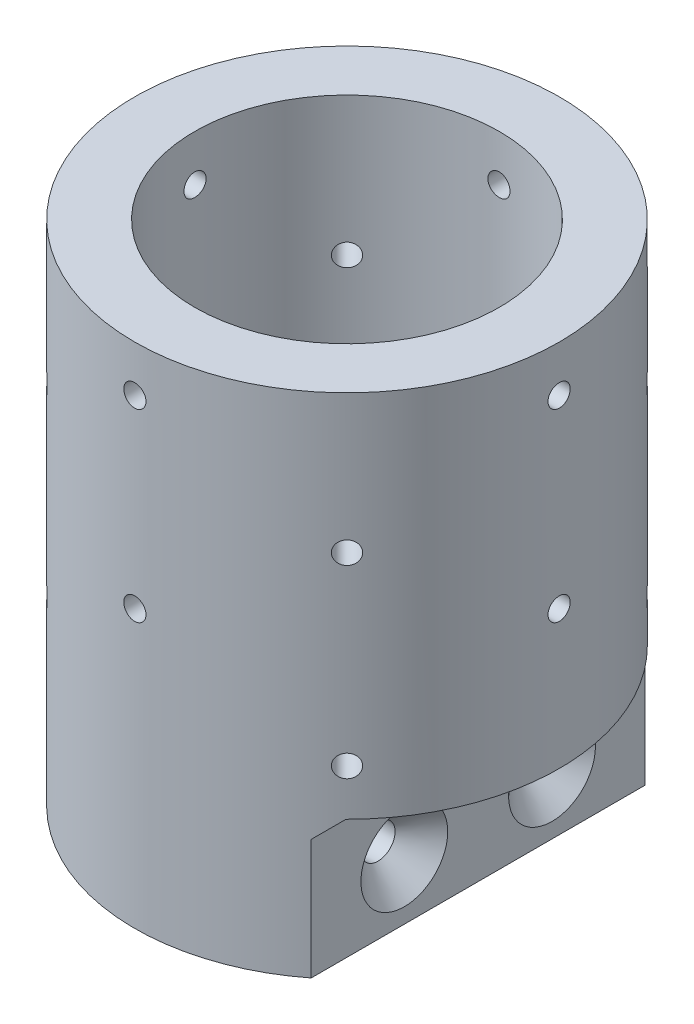
SolidWorks part; units mm, degrees
ref_plane "Спереди" through (0, 0, 0) normal (0, 0, 1) x (1, 0, 0)
ref_plane "Сверху" through (0, 0, 0) normal (0, 1, 0) x (1, 0, 0)
ref_plane "Справа" through (0, 0, 0) normal (1, 0, 0) x (0, 0, -1)
sketch "Эскиз1" plane through (0, 0, 0) normal (0, 1, 0) x (1, 0, 0)
  circle A0 centre (0, 0) radius 23
  dimension "D1" = 46
extrude "Бобышка-Вытянуть1" add sketch "Эскиз1" along normal blind 5
sketch "Эскиз2" plane through (0, 5, 0) normal (0, 1, 0) x (1, 0, 0)
  circle A0 centre (0, 0) radius 23
  circle A1 centre (0, 0) radius 16.5
  circle A2 centre (0, 0) radius 23 construction
  dimension "D1" = 33
  dimension "D2" = 0
extrude "Бобышка-Вытянуть2" add sketch "Эскиз2" along normal blind 35
chamfer "Фаска8" distance 2 angle 45 1 edges at (0, 5, 16.5)
sketch "Эскиз3" plane through (0, 0, 0) normal (1, 0, 0) x (0, 0, -1)
  line L0 (-23, 20) -> (28.0263, 20) construction
  line L1 (-23, 40) -> (-23, 0) construction
  line L2 (16.5, 40) -> (-16.5, 40) construction
  circle A1 centre (0, 35) radius 1.2
  dimension "D1" = 2.4
  dimension "D2" = 5
extrude "Вырез-Вытянуть1" cut sketch "Эскиз3" against normal through all
ref_plane "Плоскость1" through (0, 0, 0) normal (0.7071, 0, 0.7071) x (0, -1, 0)
sketch "Эскиз4" plane through (0, 0, 0) normal (0.7071, 0, 0.7071) x (0, -1, 0)
  line L0 (-20, 23) -> (-20, -30.0625) construction
  line L1 (0, 23) -> (-40, 23) construction
  line L3 (0, -23) -> (0, 23) construction
  circle A1 centre (-5, 0) radius 1.2
  dimension "D1" = 5
  dimension "D2" = 2.4
extrude "Вырез-Вытянуть2" cut sketch "Эскиз4" against normal through all from offset 16.3 offset against normal yes
pattern_circular "Круговой массив1" count 4 over 360 about axis through (0, 5, 0) along (0, -1, 0) of "Вырез-Вытянуть2"
pattern_circular "Круговой массив2" count 4 over 360 about axis through (0, 5, 0) along (0, -1, 0) of "Вырез-Вытянуть1"
pattern_linear "Линейный массив3" count 2 spacing 20 along (0, 1, 0) of "Круговой массив1"
pattern_linear "Линейный массив4" count 2 spacing 20 along (0, -1, 0) of "Круговой массив2"
sketch "Эскиз12" plane through (0, 0, 0) normal (0, -1, 0) x (1, 0, 0)
  line L1 (14.207, 18.0876) -> (14.207, -18.0876)
  line L20 (0, 15) -> (-2.7835, 17.7835)
  line L21 (-2.7835, -17.7835) -> (0, -15)
  line L22 (0, -15) -> (0, 15)
  line L23 (0, 15) -> (-2.7835, 17.7835)
  line L24 (-2.7835, -17.7835) -> (0, -15)
  line L25 (0, -15) -> (0, 15)
  circle A6 centre (0, 0) radius 23 construction
  arc A7 (14.207, 18.0876) -> (14.207, -18.0876) centre (0, 0) ccw
  arc A13 (-2.7835, 17.7835) -> (-2.7835, -17.7835) centre (0, 0) ccw
  arc A14 (-2.7835, 17.7835) -> (-2.7835, -17.7835) centre (0, 0) ccw
  dimension "D1" = 0
extrude "Бобышка-Вытянуть3" add sketch "Эскиз12" along normal blind 15 contours L1 region at (13.6153, 0, 0)
sketch "Эскиз13" plane through (0, -15, 0) normal (0, -1, 0) x (1, 0, 0)
  line L14 (-2.6786, -18.1029) -> (0.3, -15.1243)
  line L15 (0.3, 15.1243) -> (-2.6786, 18.1029)
  line L16 (0.3, -15.1243) -> (0.3, 15.1243)
  line L17 (-2.6786, -18.1029) -> (0.3, -15.1243)
  line L18 (0.3, 15.1243) -> (-2.6786, 18.1029)
  line L19 (0.3, -15.1243) -> (0.3, 15.1243)
  arc A5 (-2.6786, 18.1029) -> (-2.6786, -18.1029) centre (0, 0) ccw
  arc A6 (-2.6786, 18.1029) -> (-2.6786, -18.1029) centre (0, 0) ccw
  dimension "D1" = 0.3
extrude "Вырез-Вытянуть10" cut sketch "Эскиз13" against normal up to surface (15 mm away) up to face at (18.6035, 0, 0)
chamfer "Фаска4" distance 2 angle 45 1 edges at (14.207, 0, 0)
chamfer "Фаска6" distance 2 angle 45 4 edges at (-1.1893, 0, -16.6136) (-18.3, 0, 0) (0.3, 0, 0) (-1.1893, 0, 16.6136)
chamfer "Фаска7" distance 2 angle 45 4 edges at (-1.1893, -15, -16.6136) (-18.3, -15, 0) (-1.1893, -15, 16.6136) (0.3, -15, 0)
hole_wizard "Зенковка для винта с полупотайной головкой M41" positions "Эскиз14" profile "Эскиз15" countersink size "M4" standard "ISO" end condition through all
sketch "Эскиз14" plane through (14.207, -676.2045, -24.0267) normal (1, 0, 0) x (0, 0.0202, -0.9998)
  line L0 (-10.4265, 674.5519) -> (-10.6887, 661.5545) construction
  line L4 (-10.5576, 668.0532) -> (-20.4413, 668.0532) construction
  line L5 (-20.4413, 668.0532) -> (-1.8045, 668.0532) construction
  point P0 (-18.5576, 668.0532)
  point P19 (-2.5641, 667.7306)
sketch "Эскиз15" plane through (14.207, -8.6613, 7.9984) normal (0, 1, 0) x (0, 0, -1)
  line L0 (0, 0) -> (0, 37.207)
  line L1 (0, 37.207) -> (1.85, 37.207)
  line L2 (1.85, 37.207) -> (1.85, 2.85)
  line L3 (1.85, 2.85) -> (4.7, 0)
  line L4 (4.7, 0) -> (0, 0)
  line L5 (-1.85, 2.85) -> (-4.7, 0) construction
  line L6 (0, -6.35) -> (0, 107.95) construction
  dimension "Диаметр сквозного отверстия" = 3.7
  dimension "Глубина сквозного отверстия" = 37.207
  dimension "Диаметр передней зенковки" = 9.4
  dimension "Угол передней зенковки" = 90
